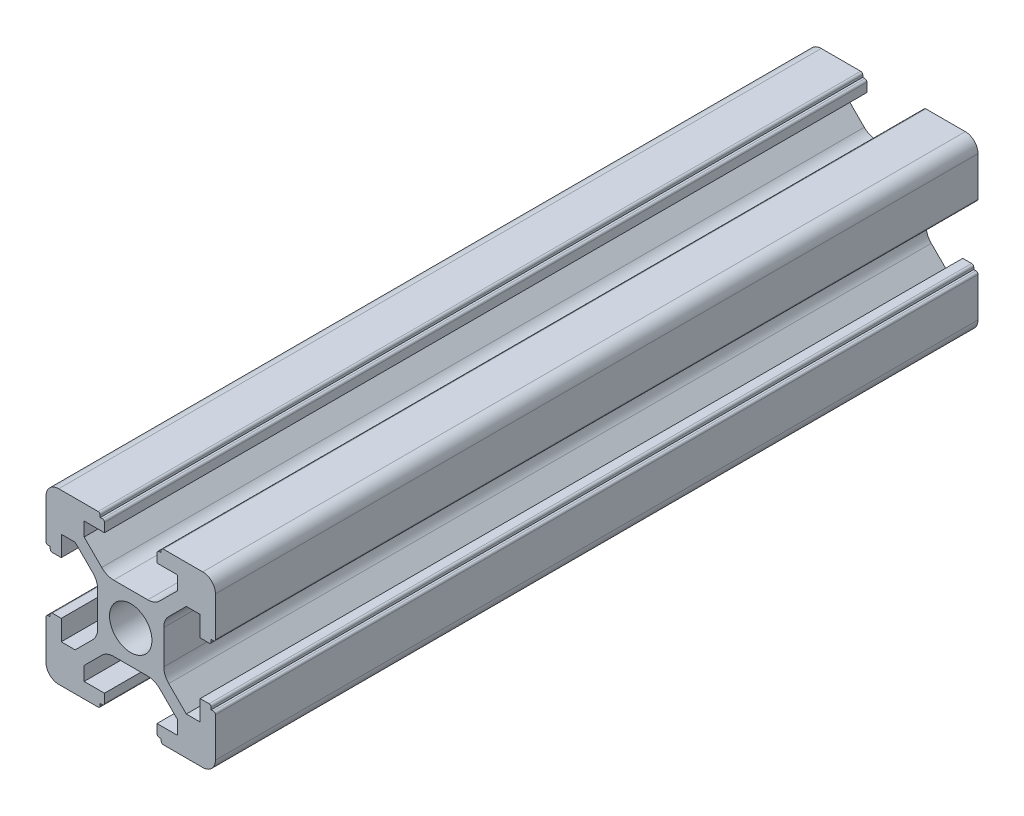
SolidWorks part; units mm, degrees
ref_plane "Front Plane" through (0, 0, 0) normal (0, 0, 1) x (1, 0, 0)
ref_plane "Top Plane" through (0, 0, 0) normal (0, 1, 0) x (1, 0, 0)
ref_plane "Right Plane" through (0, 0, 0) normal (1, 0, 0) x (0, 0, -1)
sketch "Sketch1" plane through (0, 0, 0) normal (0, 0, 1) x (1, 0, 0)
  line L0 (0, 0) -> (-10, 10) construction
  line L5 (0, 0) -> (10, 10) construction
  line L6 (22.7721, 0) -> (-22.7721, 0) construction
  line L7 (-8.5, 10) -> (-3.85, 10)
  line L8 (8.5, 10) -> (3.85, 10)
  line L9 (-3.6, 9.75) -> (-3.6, 9.5)
  line L10 (-3.6, 9.5) -> (-3.35, 9.5)
  line L11 (3.6, 9.75) -> (3.6, 9.5)
  line L12 (3.6, 9.5) -> (3.35, 9.5)
  line L13 (-3.1, 9.25) -> (-3.1, 8.2)
  line L14 (3.1, 9.25) -> (3.1, 8.2)
  line L15 (-3.1, 8.2) -> (-5.5, 8.2)
  line L16 (3.1, 8.2) -> (5.5, 8.2)
  line L17 (-3.4251, 4.4858) -> (-5.5, 6.5607)
  line L18 (-2.0109, 3.9) -> (2.0109, 3.9)
  line L19 (-5.5, 6.5607) -> (-5.5, 8.2)
  line L20 (5.5, 6.5607) -> (3.4251, 4.4858)
  line L21 (5.5, 6.5607) -> (5.5, 8.2)
  line L22 (10, 8.5) -> (10, 3.85)
  line L23 (10, -8.5) -> (10, -3.85)
  line L24 (9.75, 3.6) -> (9.5, 3.6)
  line L25 (9.5, 3.6) -> (9.5, 3.35)
  line L26 (9.75, -3.6) -> (9.5, -3.6)
  line L27 (9.5, -3.6) -> (9.5, -3.35)
  line L28 (9.25, 3.1) -> (8.2, 3.1)
  line L29 (9.25, -3.1) -> (8.2, -3.1)
  line L30 (8.2, 3.1) -> (8.2, 5.5)
  line L31 (8.2, -3.1) -> (8.2, -5.5)
  line L32 (4.4858, 3.4251) -> (6.5607, 5.5)
  line L33 (3.9, 2.0109) -> (3.9, -2.0109)
  line L34 (6.5607, 5.5) -> (8.2, 5.5)
  line L35 (6.5607, -5.5) -> (4.4858, -3.4251)
  line L36 (6.5607, -5.5) -> (8.2, -5.5)
  line L37 (8.5, -10) -> (3.85, -10)
  line L38 (-8.5, -10) -> (-3.85, -10)
  line L39 (3.6, -9.75) -> (3.6, -9.5)
  line L40 (3.6, -9.5) -> (3.35, -9.5)
  line L41 (-3.6, -9.75) -> (-3.6, -9.5)
  line L42 (-3.6, -9.5) -> (-3.35, -9.5)
  line L43 (3.1, -9.25) -> (3.1, -8.2)
  line L44 (-3.1, -9.25) -> (-3.1, -8.2)
  line L45 (3.1, -8.2) -> (5.5, -8.2)
  line L46 (-3.1, -8.2) -> (-5.5, -8.2)
  line L47 (3.4251, -4.4858) -> (5.5, -6.5607)
  line L48 (2.0109, -3.9) -> (-2.0109, -3.9)
  line L49 (5.5, -6.5607) -> (5.5, -8.2)
  line L50 (-5.5, -6.5607) -> (-3.4251, -4.4858)
  line L51 (-5.5, -6.5607) -> (-5.5, -8.2)
  line L52 (-10, -8.5) -> (-10, -3.85)
  line L53 (-10, 8.5) -> (-10, 3.85)
  line L54 (-9.75, -3.6) -> (-9.5, -3.6)
  line L55 (-9.5, -3.6) -> (-9.5, -3.35)
  line L56 (-9.75, 3.6) -> (-9.5, 3.6)
  line L57 (-9.5, 3.6) -> (-9.5, 3.35)
  line L58 (-9.25, -3.1) -> (-8.2, -3.1)
  line L59 (-9.25, 3.1) -> (-8.2, 3.1)
  line L60 (-8.2, -3.1) -> (-8.2, -5.5)
  line L61 (-8.2, 3.1) -> (-8.2, 5.5)
  line L62 (-4.4858, -3.4251) -> (-6.5607, -5.5)
  line L63 (-3.9, -2.0109) -> (-3.9, 2.0109)
  line L64 (-6.5607, -5.5) -> (-8.2, -5.5)
  line L65 (-6.5607, 5.5) -> (-4.4858, 3.4251)
  line L66 (-6.5607, 5.5) -> (-8.2, 5.5)
  circle A5 centre (0, 0) radius 2.5
  arc A6 (-8.5, -10) -> (-10, -8.5) centre (-8.5, -8.5) cw
  arc A7 (10, -8.5) -> (8.5, -10) centre (8.5, -8.5) cw
  arc A8 (8.5, 10) -> (10, 8.5) centre (8.5, 8.5) cw
  arc A9 (-8.5, 10) -> (-10, 8.5) centre (-8.5, 8.5) ccw
  arc A10 (-4.4858, -3.4251) -> (-3.9, -2.0109) centre (-5.9, -2.0109) ccw
  arc A11 (-2.0109, -3.9) -> (-3.4251, -4.4858) centre (-2.0109, -5.9) ccw
  arc A12 (3.4251, -4.4858) -> (2.0109, -3.9) centre (2.0109, -5.9) ccw
  arc A13 (3.9, -2.0109) -> (4.4858, -3.4251) centre (5.9, -2.0109) ccw
  arc A14 (4.4858, 3.4251) -> (3.9, 2.0109) centre (5.9, 2.0109) ccw
  arc A15 (3.4251, 4.4858) -> (2.0109, 3.9) centre (2.0109, 5.9) cw
  arc A16 (-3.4251, 4.4858) -> (-2.0109, 3.9) centre (-2.0109, 5.9) ccw
  arc A17 (-3.9, 2.0109) -> (-4.4858, 3.4251) centre (-5.9, 2.0109) ccw
  arc A18 (10, 3.85) -> (9.75, 3.6) centre (9.75, 3.85) cw
  arc A19 (9.5, 3.35) -> (9.25, 3.1) centre (9.25, 3.35) cw
  arc A20 (10, -3.85) -> (9.75, -3.6) centre (9.75, -3.85) ccw
  arc A21 (9.5, -3.35) -> (9.25, -3.1) centre (9.25, -3.35) ccw
  arc A22 (3.85, -10) -> (3.6, -9.75) centre (3.85, -9.75) cw
  arc A23 (3.1, -9.25) -> (3.35, -9.5) centre (3.35, -9.25) ccw
  arc A24 (-3.1, -9.25) -> (-3.35, -9.5) centre (-3.35, -9.25) cw
  arc A25 (-3.85, -10) -> (-3.6, -9.75) centre (-3.85, -9.75) ccw
  arc A26 (-10, -3.85) -> (-9.75, -3.6) centre (-9.75, -3.85) cw
  arc A27 (-9.25, -3.1) -> (-9.5, -3.35) centre (-9.25, -3.35) ccw
  arc A28 (-9.5, 3.35) -> (-9.25, 3.1) centre (-9.25, 3.35) ccw
  arc A29 (-10, 3.85) -> (-9.75, 3.6) centre (-9.75, 3.85) ccw
  arc A30 (-3.1, 9.25) -> (-3.35, 9.5) centre (-3.35, 9.25) ccw
  arc A31 (-3.85, 10) -> (-3.6, 9.75) centre (-3.85, 9.75) cw
  arc A32 (3.35, 9.5) -> (3.1, 9.25) centre (3.35, 9.25) ccw
  arc A33 (3.85, 10) -> (3.6, 9.75) centre (3.85, 9.75) ccw
  point P6 (-3.1, 9.5)
  point P7 (0, 0)
  point P28 (9.5, 3.1)
  point P46 (3.1, -9.5)
  point P63 (-9.5, -3.1)
  point P77 (0, 0)
  point P123 (-3.1, 9.5)
  point P126 (-3.6, 10)
  point P129 (3.1, 9.5)
  point P132 (3.6, 10)
  dimension "D1" = 45
  dimension "D4" = 7.2
  dimension "D2" = 5
  dimension "D13" = 1.5
  dimension "D14" = 2
  dimension "D15" = 0.25
  dimension "D3" = 20
  dimension "D5" = 0.5
  dimension "D6" = 6.2
  dimension "D7" = 1.8
  dimension "D8" = 11
  dimension "D9" = 0.75
  dimension "D10" = 6.1
  dimension "D11" = 0.75
  dimension "D12" = 4
extrude "Boss-Extrude1" add sketch "Sketch1" along normal blind 90
